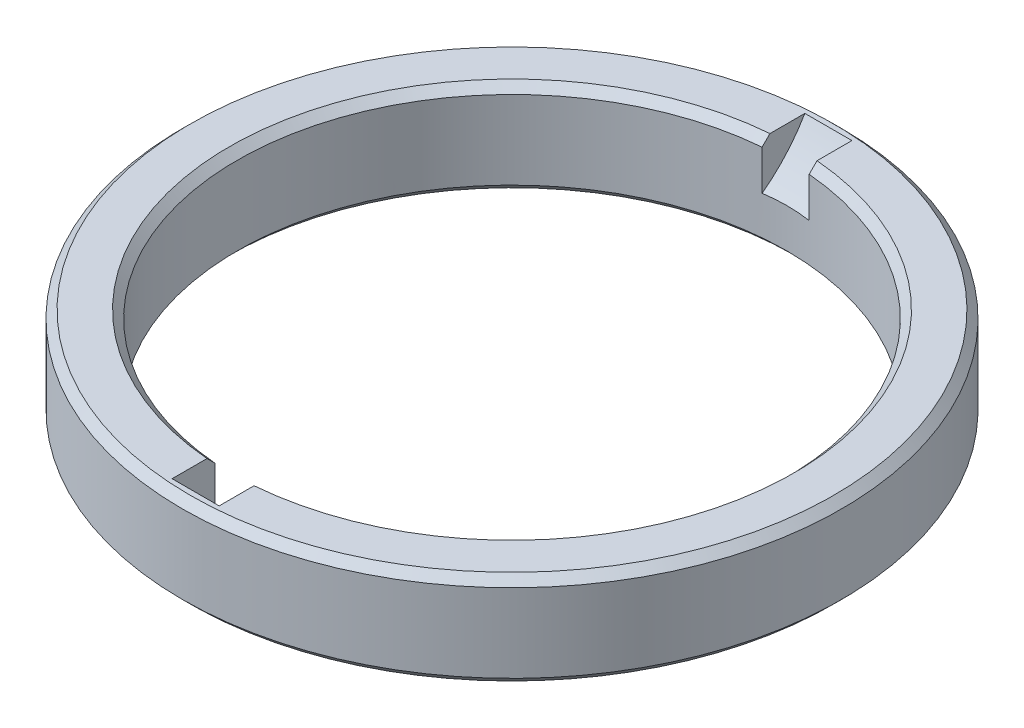
SolidWorks part; units mm, degrees
material "1060 Сплав"
ref_plane "Спереди" through (0, 0, 0) normal (0, 0, 1) x (1, 0, 0)
ref_plane "Сверху" through (0, 0, 0) normal (0, 1, 0) x (1, 0, 0)
ref_plane "Справа" through (0, 0, 0) normal (1, 0, 0) x (0, 0, -1)
sketch "Эскиз2" plane through (0, 0, 0) normal (0, 0, 1) x (1, 0, 0)
  line L0 (0, 0) -> (0, 11.7365) construction
  line L1 (17.5, 0) -> (21, 0)
  line L2 (17.5, 0) -> (17.5, 6)
  line L3 (17.5, 6) -> (21, 6)
  line L4 (21, 0) -> (21, 6)
  dimension "D1" = 35
  dimension "D2" = 42
  dimension "D3" = 6
revolve "Повернуть1" add sketch "Эскиз2" angle 360 about L0
cosmetic thread "Условное изображение резьбы1" parameters "D2"=40.344
chamfer "Фаска1" distance 0.5 angle 45 4 edges at (0, 6, -21) (0, 0, -21) (0, 0, -17.5) (0, 6, -17.5)
sketch "Эскиз4" plane through (0, 0, 0) normal (1, 0, 0) x (0, 0, -1)
  line L0 (0, 0) -> (0, 14.3824) construction
  line L1 (18, 6) -> (-18, 6) construction
  circle A0 centre (-11.5, 11) radius 10
  circle A1 centre (11.5, 11) radius 10
  dimension "D1" = 20
  dimension "D2" = 5
  dimension "D3" = 11.5
extrude "Вырез-Вытянуть2" cut sketch "Эскиз4" against normal blind 1.5 and the other way blind 1.5
